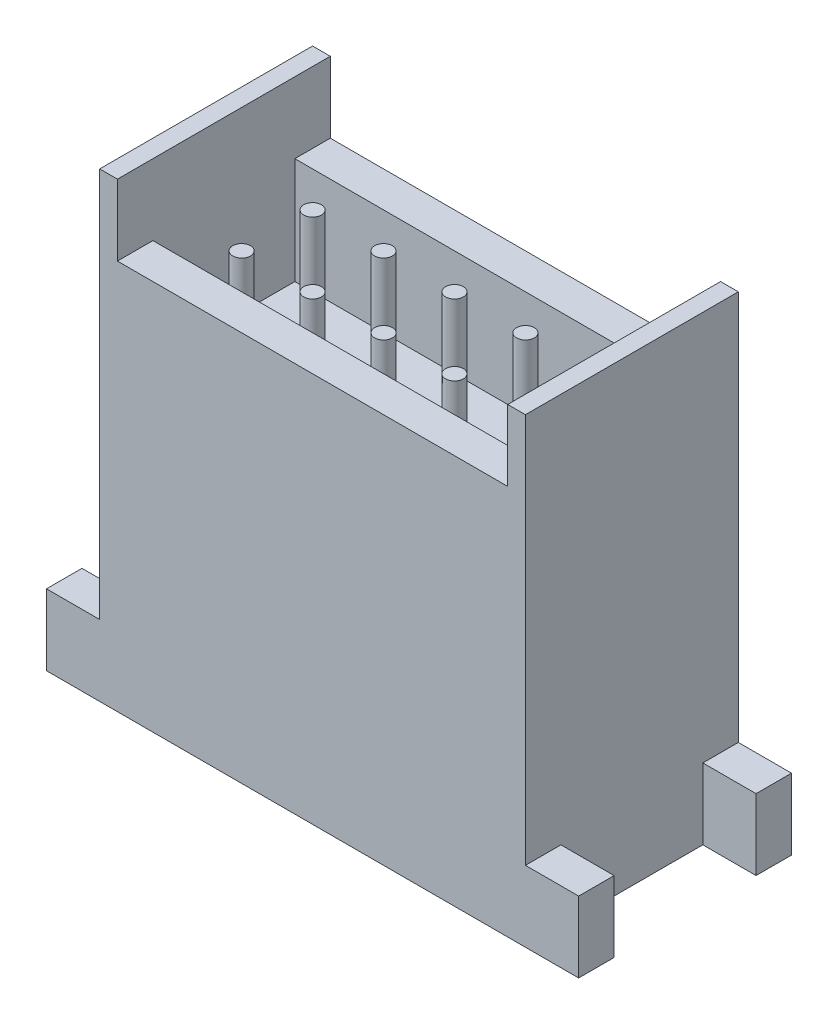
SolidWorks part; units mm, degrees
ref_plane "Front Plane" through (0, 0, 0) normal (0, 0, 1) x (1, 0, 0)
ref_plane "Top Plane" through (0, 0, 0) normal (0, 1, 0) x (1, 0, 0)
ref_plane "Right Plane" through (0, 0, 0) normal (1, 0, 0) x (0, 0, -1)
sketch "Sketch1" plane through (0, 0, 0) normal (0, 1, 0) x (1, 0, 0)
  line L1 (-6, 3) -> (6, 3)
  line L2 (-6, 3) -> (-6, -3)
  line L3 (-6, -3) -> (6, -3)
  line L4 (6, 3) -> (6, -3)
  line L5 (-6, 3) -> (6, -3) construction
  line L6 (-6, -3) -> (6, 3) construction
  point P0 (0, 0)
  dimension "D1" = 6
  dimension "D2" = 12
extrude "Boss-Extrude1" add sketch "Sketch1" along normal blind 13
sketch "Sketch2" plane through (6, 0, 0) normal (1, 0, 0) x (0, 0, -1)
  line L0 (0, 0) -> (0, 13) construction
  line L1 (-3, 0) -> (-2, 0)
  line L2 (-3, 0) -> (-3, 2)
  line L3 (-3, 2) -> (-2, 2)
  line L4 (-2, 0) -> (-2, 2)
  line L5 (-3, 0) -> (3, 0) construction
  line L6 (-3, 13) -> (3, 13) construction
  line L7 (3, 2) -> (2, 2)
  line L8 (2, 0) -> (2, 2)
  line L9 (2, 0) -> (3, 0)
  line L10 (3, 0) -> (3, 2)
  line M1 (-3, 0) -> (3, 0)
  line M2 (3, 0) -> (3, 13)
  line M4 (-3, 13) -> (-3, 0)
  dimension "D1" = 2
  dimension "D2" = 1
extrude "Boss-Extrude2" add sketch "Sketch2" along normal blind 1.5 contours L8 L7 M1 M2 | L4 L3 M1 M4 region at (6, 1, 2.5) region at (6, 1, -2.5)
mirror "Mirror1" about plane through (0, 0, 0) normal (1, 0, 0) of "Boss-Extrude2"
sketch "Sketch3" plane through (0, 13, 0) normal (0, 1, 0) x (1, 0, 0)
  line L0 (-6, -3) -> (6, -3) construction
  line L1 (-5.5, 2) -> (5.5, 2)
  line L2 (-5.5, 2) -> (-5.5, -2)
  line L3 (-5.5, -2) -> (5.5, -2)
  line L4 (5.5, 2) -> (5.5, -2)
  line L5 (-5.5, 2) -> (5.5, -2) construction
  line L6 (-5.5, -2) -> (5.5, 2) construction
  line L7 (6, -3) -> (6, 3) construction
  point P0 (0, 0)
  dimension "D1" = 1
  dimension "D2" = 0.5
extrude "Cut-Extrude1" cut sketch "Sketch3" against normal blind 5
sketch "Sketch4" plane through (0, 13, 0) normal (0, 1, 0) x (1, 0, 0)
  line L0 (6, 3) -> (-6, 3) construction
  line L1 (-5.5, 2) -> (5.5, 2)
  line L2 (-5.5, 2) -> (-5.5, 3)
  line L3 (-5.5, 3) -> (5.5, 3)
  line L4 (5.5, 2) -> (5.5, 3)
  line L5 (5.5, -2) -> (5.5, 2) construction
  line L6 (-6, -3) -> (6, -3) construction
  line L7 (-5.5, -2) -> (5.5, -2)
  line L8 (-5.5, -2) -> (-5.5, -3)
  line L9 (-5.5, -3) -> (5.5, -3)
  line L10 (5.5, -2) -> (5.5, -3)
extrude "Cut-Extrude2" cut sketch "Sketch4" against normal blind 2
sketch "Sketch5" plane through (0, 8, 0) normal (0, 1, 0) x (1, 0, 0)
  line L0 (0, 0) -> (0, 2) construction
  line L3 (-5.5, 0) -> (5.5, 0) construction
  line L4 (-5.5, 2) -> (-5.5, -2) construction
  line L5 (5.5, -2) -> (5.5, 2) construction
  line L6 (5.5, 2) -> (-5.5, 2) construction
  line L7 (0, 0) -> (0, -2) construction
  line L8 (-5.5, -2) -> (5.5, -2) construction
  line L9 (0, 1) -> (2, 1) construction
  circle A0 centre (0, 1) radius 0.25
  circle A1 centre (2, 1) radius 0.25
  circle A2 centre (4, 1) radius 0.25
  circle A3 centre (-4, 1) radius 0.25
  circle A4 centre (-2, 1) radius 0.25
  circle A5 centre (4, -1) radius 0.25
  circle A6 centre (2, -1) radius 0.25
  circle A7 centre (0, -1) radius 0.25
  circle A8 centre (-2, -1) radius 0.25
  circle A9 centre (-4, -1) radius 0.25
  dimension "D1" = 0.5
  dimension "D3" = 2
  dimension "D4" = 1
  dimension "D2" = 3
extrude "Boss-Extrude3" add sketch "Sketch5" along normal blind 3
